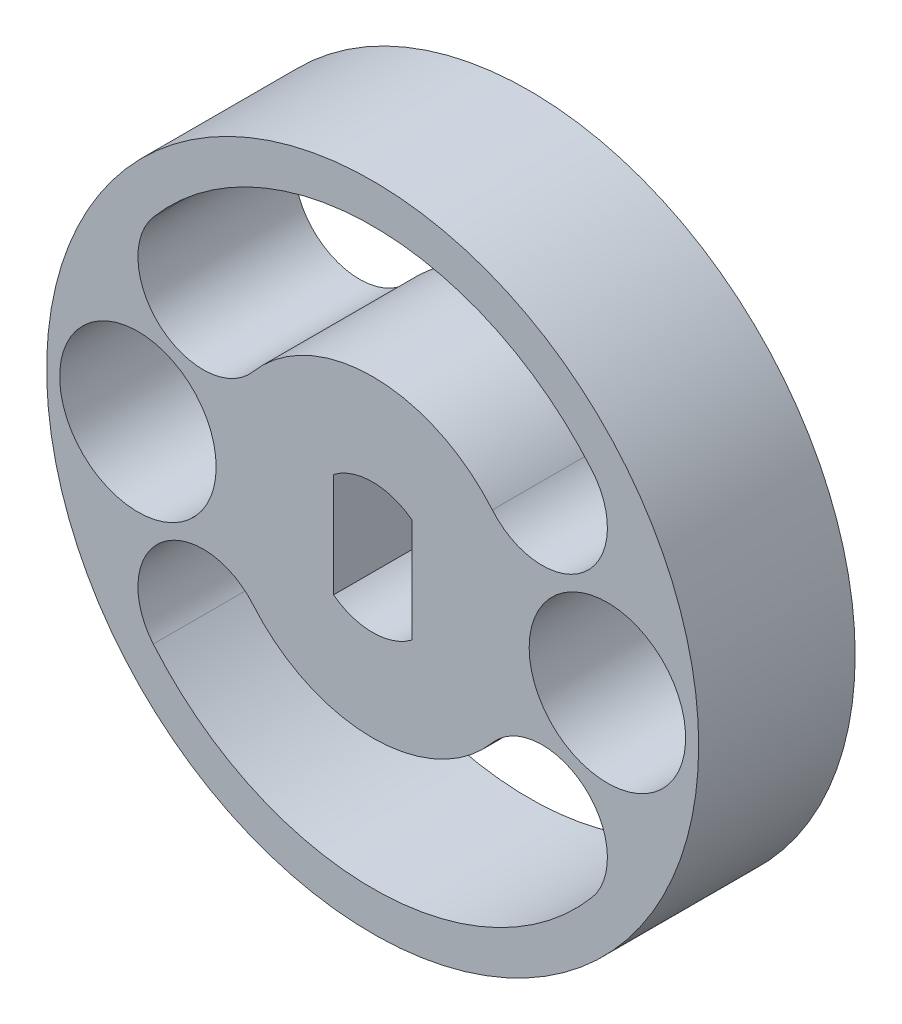
SolidWorks part; units mm, degrees
ref_plane "Front Plane" through (0, 0, 0) normal (0, 0, 1) x (1, 0, 0)
ref_plane "Top Plane" through (0, 0, 0) normal (0, 1, 0) x (1, 0, 0)
ref_plane "Right Plane" through (0, 0, 0) normal (1, 0, 0) x (0, 0, -1)
sketch "Sketch1" plane through (0, 0, 0) normal (0, 0, 1) x (1, 0, 0)
  line L0 (1500, 2000) -> (1500, 0)
  line L1 (1500, 0) -> (6000, 0)
  line L2 (12000, 0) -> (12500, 0)
  line L3 (0, 12500) -> (0, 2500)
  arc A0 (0, 2500) -> (1500, 2000) centre (0, 0) cw
  arc A1 (6000, 0) -> (12000, 0) centre (9000, 0) cw
  arc A2 (12500, 0) -> (0, 12500) centre (0, 0) ccw
  point P11 (0, 0)
  point P12 (15325.7304, 0)
  point P13 (0, 12176.4218)
  point P14 (15204.6428, 0)
  point P15 (0, 0)
  point P16 (0, 0)
  point P17 (0, 0)
  point P18 (0, 0)
  dimension "D1" = 3000
  dimension "D2" = 2500
  dimension "D4" = 12500
  dimension "D5" = 1500
  dimension "D3" = 9000
  dimension "D6" = 12500
extrude "Boss-Extrude1" add sketch "Sketch1" along normal blind 6000
mirror "Mirror4" about plane through (0, 12500, 6000) normal (1, 0, 0) of bodies 101
sketch "Sketch2" plane through (0, 0, 6000) normal (0, 0, 1) x (1, 0, 0)
  line L0 (-6500, 5477.2256) -> (6500, 5477.2256) construction
  arc A0 (-6500, 5477.2256) -> (6500, 5477.2256) centre (0, 0) cw construction
  arc A1 (8411.7647, 7088.1743) -> (-8411.7647, 7088.1743) centre (0, 0) ccw
  arc A2 (4588.2353, 3866.2769) -> (-4588.2353, 3866.2769) centre (0, 0) ccw
  arc A3 (4588.2353, 3866.2769) -> (8411.7647, 7088.1743) centre (6500, 5477.2256) ccw
  arc A4 (-8411.7647, 7088.1743) -> (-4588.2353, 3866.2769) centre (-6500, 5477.2256) ccw
  point P5 (0, 8500)
  point P10 (-6587.0852, 5788.3714)
  point P11 (0, 8966.5068)
  point P12 (-6500, 5477.2256)
  point P13 (0, 6000)
  dimension "D2" = 13000
  dimension "D1" = 8500
  dimension "D3" = 6000
extrude "Cut-Extrude1" cut sketch "Sketch2" against normal through all
mirror "Mirror5" about plane through (-1500, 0, 6000) normal (0, 1, 0) of bodies 106
